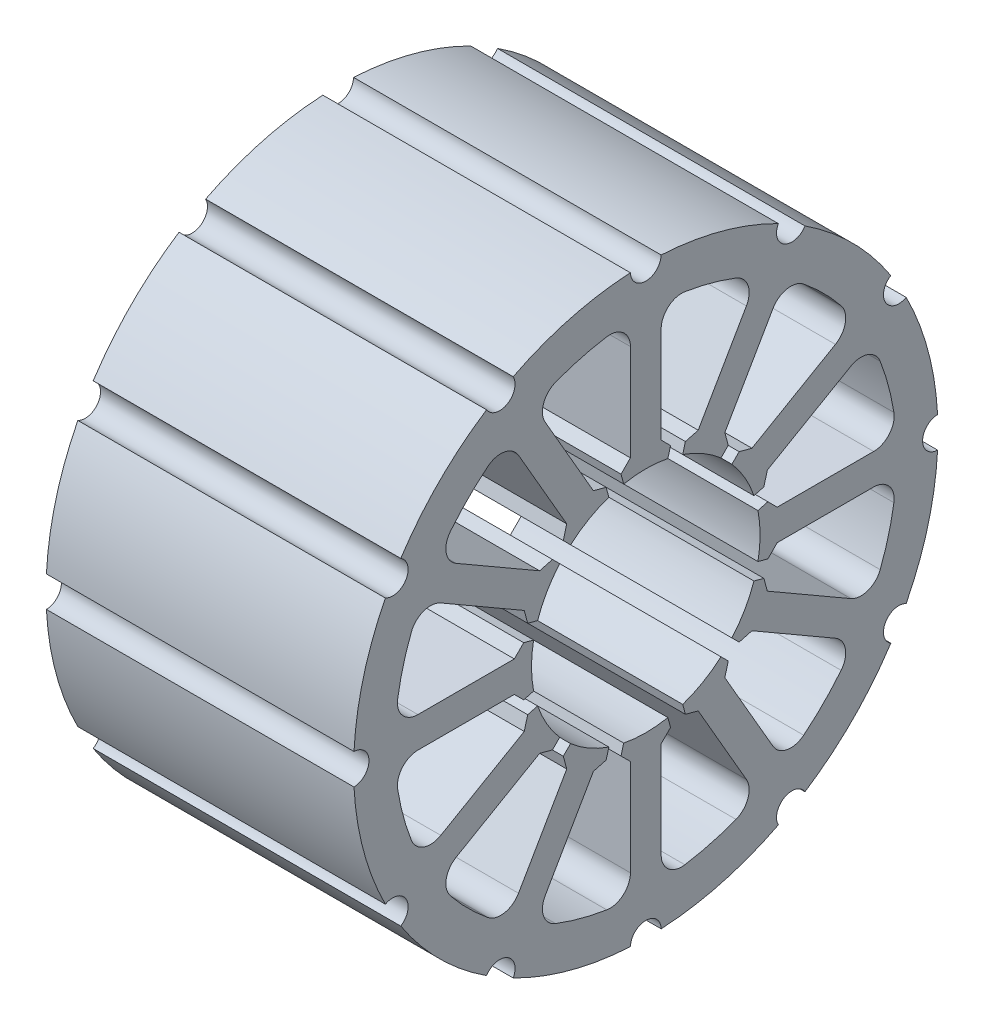
SolidWorks part; units mm, degrees
material "Vacoflux 50"
ref_plane "Front Plane" through (0, 0, 0) normal (0, 0, 1) x (1, 0, 0)
ref_plane "Top Plane" through (0, 0, 0) normal (0, 1, 0) x (1, 0, 0)
ref_plane "Right Plane" through (0, 0, 0) normal (1, 0, 0) x (0, 0, -1)
sketch "Sketch3" plane through (0, 0, 0) normal (1, 0, 0) x (0, 0, -1)
  line L0 (-14.25, 24.6817) -> (-5.575, 9.6562)
  line L1 (0, 28.5) -> (0, 11.15)
  line L2 (-1.5, 22.2261) -> (-1.5, 12.8219)
  line L3 (-9.814, 19.9984) -> (-5.1119, 11.8541)
  line L4 (-1.5, 12.8219) -> (-2.4142, 11.9077)
  line L5 (-2.4142, 11.9077) -> (-2.1549, 10.9398)
  line L6 (-3.6037, 10.5516) -> (-3.8631, 11.5195)
  line L7 (-3.8631, 11.5195) -> (-5.1119, 11.8541)
  line L8 (0, 0) -> (-6.4601, 24.1093) construction
  arc A0 (0, 28.5) -> (-14.25, 24.6817) centre (0, 0) ccw
  arc A1 (0, 11.15) -> (-5.575, 9.6562) centre (0, 0) ccw construction
  arc A2 (-8.8004, 22.8649) -> (-3.8111, 24.2018) centre (0, 0) cw
  arc A3 (-5.575, 9.6562) -> (-3.6037, 10.5516) centre (0, 0) cw
  arc A4 (-2.1549, 10.9398) -> (0, 11.15) centre (0, 0) cw
  arc A5 (-1.5, 22.2261) -> (-3.8111, 24.2018) centre (-3.5, 22.2261) ccw
  arc A6 (-8.8004, 22.8649) -> (-9.814, 19.9984) centre (-8.082, 20.9984) ccw
  arc A7 (-2.4142, 11.9077) -> (-3.8631, 11.5195) centre (0, 0) ccw construction
  dimension "D1" = 28.5
  dimension "D2" = 11.15
  dimension "D7" = 2
  dimension "D3" = 30
  dimension "D4" = 1.5
  dimension "D5" = 1.5
  dimension "D6" = 4
  dimension "D8" = 15
  dimension "D9" = 1.5
  dimension "D10" = 0.75
  dimension "D11" = 1
  dimension "D12" = 120
  dimension "D13" = 120
extrude "Boss-Extrude1" add sketch "Sketch3" along normal blind 30
ref_axis "Axis1" through (-2, 0, 0) along (1, 0, 0)
pattern_circular "CirPattern1" count 12 over 360 about axis through (-2, 0, 0) along (1, 0, 0) of "Boss-Extrude1"
sketch "Sketch4" plane through (0, 0, 0) normal (1, 0, 0) x (0, 0, -1)
  line L0 (0, 28.5) -> (0, 0) construction
  circle A0 centre (0, 28.5) radius 1.5
  dimension "D1" = 28.5
  dimension "D2" = 3
extrude "Cut-Extrude1" cut sketch "Sketch4" along normal blind 30 contours A0
pattern_circular "CirPattern2" count 12 over 360 about axis through (-2, 0, 0) along (1, 0, 0) of "Cut-Extrude1" reverse direction yes
equation "\"OuterDiam\"= 57"
equation "\"InnerDiam\"= 22.3"
equation "\"Length\"= 30"
equation "\"slots\"= 12"
equation "\"ppairs\"= 2"
equation "\"hYoke\"= 4"
equation "\"wTooth\"= 3"
equation "\"D1@Sketch3\"=\"OuterDiam\"/2"
equation "\"D2@Sketch3\"=\"InnerDiam\"/2"
equation "\"D3@Sketch3\"=360deg/\"slots\""
equation "\"D5@Sketch3\"=\"wTooth\"/2"
equation "\"D4@Sketch3\"=\"wTooth\"/2"
equation "\"D6@Sketch3\"=\"hYoke\""
equation "\"D1@Boss-Extrude1\"=\"Length\""
equation "\"D1@CirPattern1\"=\"slots\""
equation "\"D8@Sketch3\"=360deg/\"slots\"/2"
equation "\"D10@Sketch3\"=\"D9@Sketch3\"/2"
equation "\"D13@Sketch3\"=\"D12@Sketch3\""
equation "\"D1@Sketch4\"=\"OuterDiam\"/2"
equation "\"D1@Cut-Extrude1\"=\"Length\""
equation "\"D1@CirPattern2\"=\"slots\""
